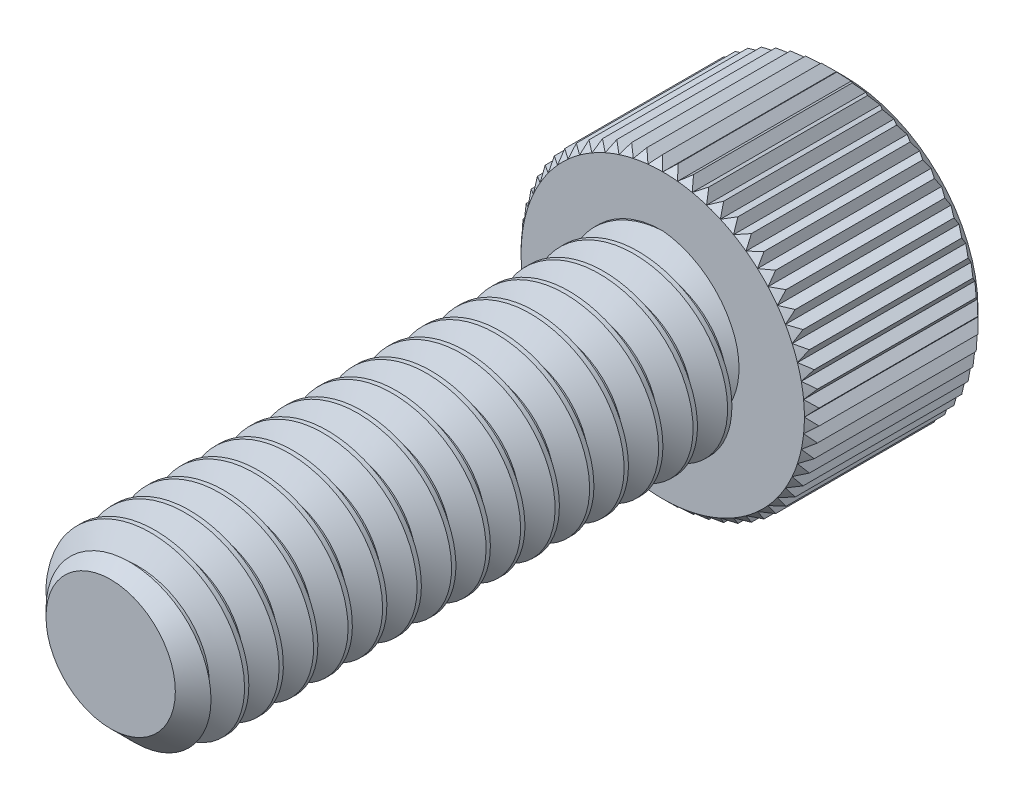
SolidWorks part; units mm, degrees
note: '?' marks a value the reader was unsure of.
ref_plane "Front Plane" through (0, 0, 0) normal (0, 0, 1) x (1, 0, 0)
ref_plane "Top Plane" through (0, 0, 0) normal (0, 1, 0) x (1, 0, 0)
ref_plane "Right Plane" through (0, 0, 0) normal (1, 0, 0) x (0, 0, -1)
sketch "Sketch0" plane through (0, 0, 0) normal (1, 0, 0) x (0, 0, -1)
  line L0 (0, 0) -> (12.7, 0) construction
  point P2 (16.8656, 0)
  point P4 (0, 0)
  dimension "D1" = 12.7
  dimension "D2" = 4.1656
  dimension "Min Thread" = 0
sketch "Sketch1" plane through (0, 0, 0) normal (0, 0, 1) x (1, 0, 0)
  circle A0 centre (0, 0) radius 2.0828
  dimension "OD" = 4.1656
extrude "Extrude1" add sketch "Sketch1" against normal blind 12.7
sketch "Sketch2" plane through (0, 0, 0) normal (0, 0, 1) x (1, 0, 0)
  circle A0 centre (0, 0) radius 2.0828 construction
  circle A1 centre (0, 0) radius 2.0828
curve "Helix/Spiral1" pitch 0.7937 height 13.4937 turns 17 parameters "pitch"=0.7937
chamfer "Chamfer3" distance 0.5953 angle 45 1 edges at (2.0828, 0, 0)
sketch "Sketch3" plane through (0, 0, 0) normal (1, 0, 0) x (0, 0, -1)
  line L0 (-0.6945, 2.0828) -> (-0.3969, 1.5672)
  line L1 (-0.3969, 1.5672) -> (-0.2977, 1.5672)
  line L2 (-0.2977, 1.5672) -> (0, 2.0828)
  line L3 (-0.6945, 2.0828) -> (0, 2.0828)
  line L4 (-0.3473, 2.0828) -> (-0.3473, 1.5672) construction
  line L5 (-0.5457, 1.825) -> (-0.1488, 1.825) construction
  line L6 (0, 2.0828) -> (0, -2.0828) construction
  dimension "D1" = 0.0992
  dimension "D2" = 0.3969
  dimension "D3" = 60
sweep "Cut-Sweep1" cut profiles "Sketch3" path "Helix/Spiral1"
sketch "Sketch5" plane through (0, 0, 0) normal (1, 0, 0) x (0, 0, -1)
  line L0 (12.7, -1.5805) -> (12.7, 1.4861) construction
  line L1 (12.7, 2.0828) -> (0, 2.0828)
  line L2 (12.7, 2.0828) -> (12.7, 0)
  line L3 (12.7, 0) -> (-0.7581, 0)
  line L4 (0, 0) -> (12.7, 0) construction
  line L5 (0, 2.0828) -> (-0.7581, 0)
  line L6 (0, 0) -> (15.24, 0) construction
  dimension "D1" = 70
  dimension "D3" = 2.54
revolve "partially thread" [suppressed] add sketch "Sketch5" angle 360 about L6
sketch "Sketch6" plane through (0, 0, -12.7) normal (0, 0, -1) x (-1, 0, 0)
  circle A0 centre (0, 0) radius 3.429
  dimension "head dia" = 6.858
extrude "Extrude2" add sketch "Sketch6" along normal blind 4.1656
sketch "Sketch7" plane through (0, 0, -16.8656) normal (0, 0, -1) x (-1, 0, 0)
  line L1 (0, 2.0622) -> (-1.7859, 1.0311)
  line L2 (-1.7859, 1.0311) -> (-1.7859, -1.0311)
  line L3 (-1.7859, -1.0311) -> (0, -2.0622)
  line L4 (0, -2.0622) -> (1.7859, -1.0311)
  line L5 (1.7859, -1.0311) -> (1.7859, 1.0311)
  line L6 (1.7859, 1.0311) -> (0, 2.0622)
  circle A0 centre (0, 0) radius 1.7859 construction
  dimension "hex dia" = 3.5719
extrude "Cut-Extrude1" cut sketch "Sketch7" against normal blind 2.6789
sketch "Sketch8" plane through (0, 0, -16.8656) normal (0, 0, -1) x (-1, 0, 0)
  circle A0 centre (0, 0) radius 2.0622
extrude "Cut-Extrude2" cut sketch "Sketch8" against normal through all draft 45
chamfer "Chamfer1" distance 0.3429 angle 45 1 edges at (-3.429, 0, -16.8656)
chamfer "Chamfer2" distance 0.1714 angle 45 1 edges at (-3.429, 0, -12.7)
sketch "Sketch9" plane through (0, 0, 0) normal (1, 0, 0) x (0, 0, -1)
  line L0 (0, 2.0828) -> (0, -2.0828) construction
  line L1 (1.9844, 2.0828) -> (1.9844, -2.0828) construction
  line L2 (16.8656, 3.429) -> (16.8656, -3.429) construction
  line L3 (12.7, 3.429) -> (12.7, -3.429) construction
  line L4 (12.7, 3.2576) -> (12.7, -3.2576) construction
  line L5 (16.8656, -3.0861) -> (16.8656, 3.0861) construction
  line L6 (12.7, -3.429) -> (12.7, 3.429) construction
  line L7 (0, 1.4875) -> (0, -1.4875) construction
  line L8 (-0.6945, 2.0828) -> (0, 2.0828) construction
  line L9 (1.9844, 0) -> (0, 0) construction
  dimension "D1" = 1.9844
sketch "Sketch10" plane through (0, 0, -12.7) normal (0, 0, 1) x (1, 0, 0)
  line L0 (-0.369, 3.6005) -> (0, 3.2576)
  line L1 (0, 3.2576) -> (0.369, 3.6005)
  line L2 (0, 3.2576) -> (0, 3.6005) construction
  line L3 (-0.369, 3.6005) -> (0.369, 3.6005)
  line L4 (0, -3.7667) -> (0, 3.7667) construction
  line L5 (0, 0) -> (0.1795, 3.4243) construction
  line L6 (-0.1795, 3.4243) -> (0, 0) construction
  circle A2 centre (0, 0) radius 3.429 construction
  circle A5 centre (0, 0) radius 3.2576 construction
  dimension "D1" = 6
  dimension "D2" = 0.3429
extrude "Cut-Extrude3" cut sketch "Sketch10" against normal through all
pattern_circular "CirPattern1" count 60 over 360 about axis through (0, 0, 0) along (0, 0, 1) of "Cut-Extrude3"
ref_plane "Contact Plane 1" through (0, 0, -12.7) normal (0, 0, 1) x (1, 0, 0)
ref_axis "Center Axis 1" through (0, 0, 0.8878) along (0, 0, -1)?
equation "\"D3@Helix/Spiral1\" = \"screw length@Extrude1\"+\"pitch@Helix/Spiral1\""
equation "\"D1@Sketch3\" = \"pitch@Helix/Spiral1\"*.125"
equation "\"D2@Sketch3\" = \"pitch@Helix/Spiral1\"*.5"
equation "\"D1@Cut-Extrude1\" = \"hex dia@Sketch7\"*.75"
equation "\"D1@Chamfer1\" = \"head dia@Sketch6\"*.05"
equation "\"D1@Sketch9\" = \"pitch@Helix/Spiral1\"*2.50"
equation "\"D1@Chamfer2\" = \"D1@Chamfer1\"/2"
equation "\"D1@Chamfer3\" = \"pitch@Helix/Spiral1\"*.750"
equation "\"D1@Sketch0\" = \"screw length@Extrude1\""
equation "\"D2@Sketch0\" = \"head depth@Extrude2\""
equation "\"D2@Sketch10\"=\"D1@Chamfer1\""
equation "\"D1@CirPattern1\"=\"D3@CirPattern1\"/\"D1@Sketch10\""
